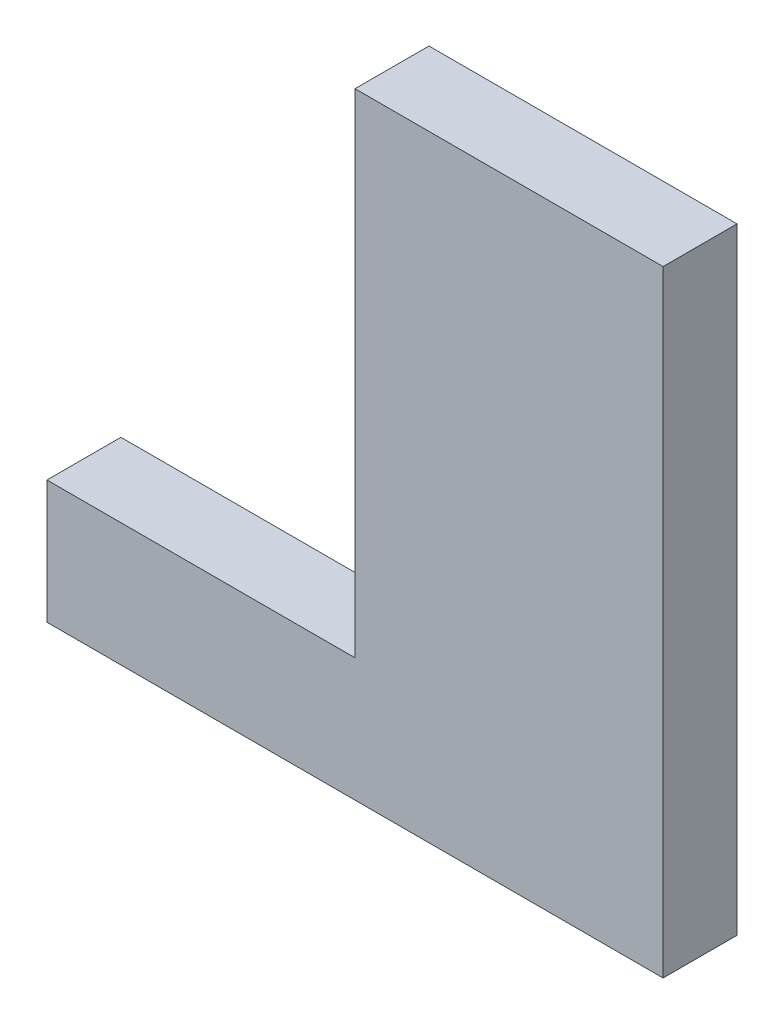
SolidWorks part; units mm, degrees
ref_plane "Front Plane" through (0, 0, 0) normal (0, 0, 1) x (1, 0, 0)
ref_plane "Top Plane" through (0, 0, 0) normal (0, 1, 0) x (1, 0, 0)
ref_plane "Right Plane" through (0, 0, 0) normal (1, 0, 0) x (0, 0, -1)
sketch "Sketch1" plane through (0, 0, 0) normal (0, 1, 0) x (1, 0, 0)
  line L0 (0, 1.5) -> (0, -1.5) construction
  line L1 (-12.5, -1.5) -> (12.5, -1.5)
  line L2 (-12.5, -1.5) -> (-12.5, 1.5)
  line L3 (-12.5, 1.5) -> (12.5, 1.5)
  line L4 (12.5, -1.5) -> (12.5, 1.5)
  point P0 (0, 0)
  dimension "D1" = 3
  dimension "D2" = 25
extrude "Boss-Extrude1" add sketch "Sketch1" along normal blind 25 contours L3 L0 L1 L4 region at (6.25, 0, 0)
extrude "Boss-Extrude2" add sketch "Sketch1<3>" along normal blind 5 contours L0 L3 L2 L1 region at (-6.25, 0, 0)
sketch "Sketch1<3>" plane through (0, 0, 0) normal (0, 1, 0) x (1, 0, 0) same geometry as "Sketch1"
